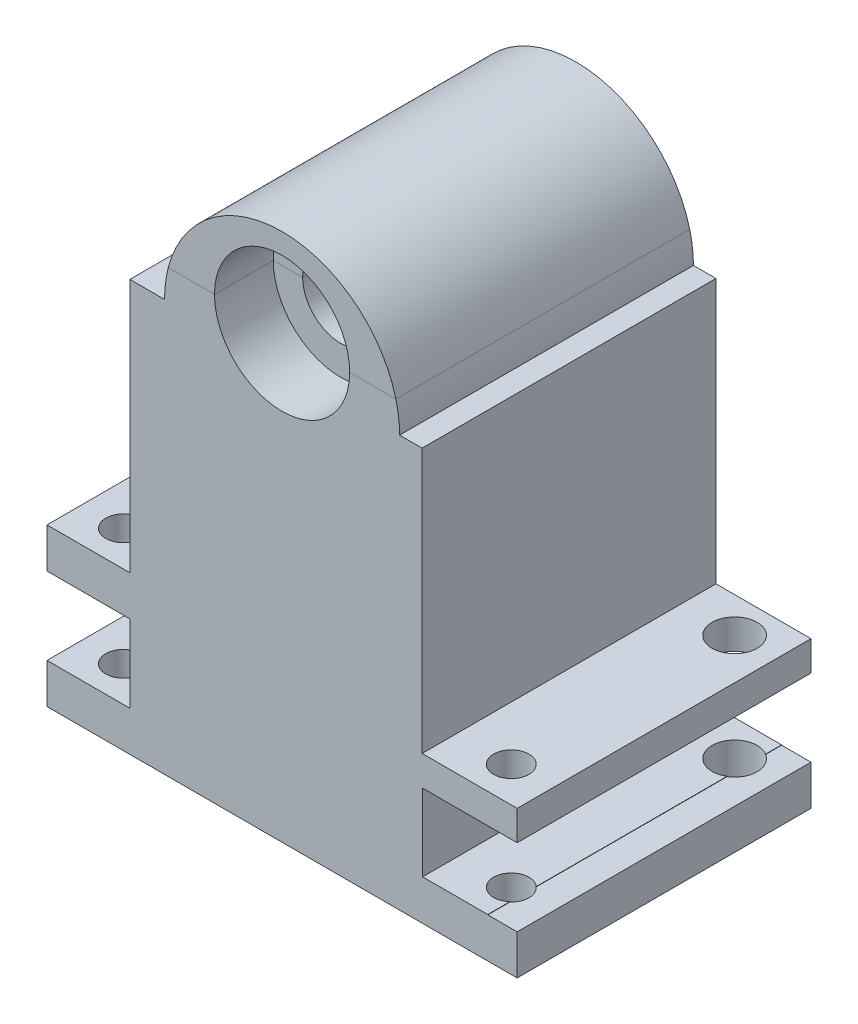
SolidWorks part; units mm, degrees
ref_plane "Plan de face" through (0, 0, 0) normal (0, 0, 1) x (1, 0, 0)
ref_plane "Plan de dessus" through (0, 0, 0) normal (0, 1, 0) x (1, 0, 0)
ref_plane "Plan de droite" through (0, 0, 0) normal (1, 0, 0) x (0, 0, -1)
sketch "Esquisse1" plane through (0, 0, 0) normal (0, 0, 1) x (1, 0, 0)
  line L0 (0, 0) -> (700, 0)
  line L1 (700, 0) -> (700, 450)
  line L2 (700, 450) -> (550, 450)
  line L3 (0, 0) -> (0, 450)
  line L4 (0, 450) -> (150, 450)
  arc A0 (550, 450) -> (150, 450) centre (350, 450) ccw
  dimension "D3" = 200
  dimension "D1" = 700
  dimension "D2" = 450
  dimension "D4" = 150
extrude "Boss.-Extru.1" add sketch "Esquisse1" along normal blind 500
sketch "Esquisse2" plane through (0, 0, 0) normal (0, -1, 0) x (1, 0, 0)
  line L0 (700, 500) -> (700, 0)
  line L1 (700, 0) -> (0, 0)
  line L2 (0, 0) -> (0, 500)
  line L3 (0, 500) -> (700, 500) construction
  line L4 (0, 500) -> (0, 0) construction
  line L5 (0, 500) -> (700, 500)
extrude "Boss.-Extru.2" add sketch "Esquisse2" along normal blind 250
sketch "Esquisse3" plane through (0, 0, 0) normal (0, 0, -1) x (-1, 0, 0)
  circle A0 centre (-350, 500) radius 65
extrude "Enlèv. mat.-Extru.1" cut sketch "Esquisse3" against normal blind 500
sketch "Esquisse4" plane through (0, 0, 0) normal (0, 0, -1) x (-1, 0, 0)
  line L0 (0, -50.3189) -> (-91.0727, -50.3189)
  line L1 (0, 450) -> (0, -250) construction
  line L2 (-91.0727, -50.3189) -> (-91.0727, -181.9886)
  line L3 (-91.0727, -181.9886) -> (0, -181.9886)
  line L4 (0, -181.9886) -> (0, -50.3189)
extrude "Enlèv. mat.-Extru.2" cut sketch "Esquisse4" against normal blind 500
sketch "Esquisse5" plane through (0, 0, 0) normal (0, 0, -1) x (-1, 0, 0)
  line L0 (-700, -181.4044) -> (-589.1123, -181.4044)
  line L1 (-700, -250) -> (-700, 450) construction
  line L2 (-589.1123, -181.4044) -> (-589.1123, -50.6587)
  line L3 (-589.1123, -50.6587) -> (-700, -50.6587)
  line L4 (-700, -50.6587) -> (-700, -181.4044)
extrude "Enlèv. mat.-Extru.3" cut sketch "Esquisse5" against normal blind 500
ref_plane "Plan1" through (0, 500, 0) normal (0, -1, 0) x (-1, 0, 0)
sketch "Esquisse6" plane through (0, 0, 500) normal (0, 0, 1) x (1, 0, 0)
  circle A0 centre (350, 500) radius 115
  circle A1 centre (350, 500) radius 65
extrude "Enlèv. mat.-Extru.4" cut sketch "Esquisse6" against normal blind 100
split "Fractionner2" trim tools "Plan1" bodies to split 108 resulting bodies 109 110
sketch "Esquisse7" plane through (0, 0, 0) normal (0, 0, -1) x (-1, 0, 0)
  circle A0 centre (-350, 500) radius 115
  circle A1 centre (-350, 500) radius 65
extrude "Enlèv. mat.-Extru.5" cut sketch "Esquisse7" against normal blind 100
sketch "Esquisse9" plane through (0, 0, 500) normal (0, 0, 1) x (1, 0, 0)
  line L1 (700, 450) -> (750, 450)
  line L2 (700, 450) -> (700, -50.6587)
  line L3 (700, -50.6587) -> (750, -50.6587)
  line L4 (750, 450) -> (750, -50.6587)
  line L5 (700, -250) -> (750, -250)
  line L6 (700, -250) -> (700, -181.9464)
  line L7 (700, -181.9464) -> (750, -181.9464)
  line L8 (750, -250) -> (750, -181.9464)
  line L9 (0, -50.3189) -> (-50, -50.3189)
  line L10 (0, -50.3189) -> (0, 450)
  line L11 (0, 450) -> (-50, 450)
  line L12 (-50, -50.3189) -> (-50, 450)
  line L13 (0, -181.9886) -> (-50, -181.9886)
  line L14 (0, -181.9886) -> (0, -250)
  line L15 (0, -250) -> (-50, -250)
  line L16 (-50, -181.9886) -> (-50, -250)
  dimension "D1" = 50
  dimension "D2" = 50
extrude "Boss.-Extru.3" add sketch "Esquisse9" against normal blind 500
sketch "Esquisse10" plane through (0, 0, 500) normal (0, 0, 1) x (1, 0, 0)
  line L0 (91.0727, -50.3189) -> (91.0727, 450)
  line L1 (150, 450) -> (-50, 450) construction
  line L2 (91.0727, 450) -> (-50, 450)
  line L3 (-50, 450) -> (-50, 17.6911)
  line L4 (-50, 450) -> (-50, -50.3189) construction
  line L5 (-50, 17.6911) -> (91.0727, 17.6911)
  line L8 (750, 0) -> (588.2822, 0)
  line L9 (750, -50.6587) -> (750, 450) construction
  line L10 (588.2822, 0) -> (588.2822, 450)
  line L11 (750, 450) -> (550, 450) construction
  line L12 (588.2822, 450) -> (750, 450)
  line L13 (750, 450) -> (750, 0)
  line M3 (150, 450) -> (-50, 450)
  line M4 (-50, 450) -> (-50, -50.3189)
  line M16 (750, -50.6587) -> (750, 450)
  line M17 (750, 450) -> (550, 450)
  dimension "D1" = 68.01
extrude "Enlèv. mat.-Extru.6" cut sketch "Esquisse10" against normal blind 500 contours L10 L8 M16 M17 | L5 L0 M4 M3 region at (20.5364, 233.8456, 500) region at (669.1411, 225, 500)
sketch "Esquisse11" plane through (0, 17.6911, 0) normal (0, 1, 0) x (1, 0, 0)
  line L0 (-50, 0) -> (91.0727, 0) construction
  line L1 (-50, 0) -> (-50, -500) construction
  line L2 (-50, -500) -> (91.0727, -500) construction
  circle A0 centre (20, -60) radius 30
  circle A1 centre (20, -440) radius 30
  point P8 (0, 0)
  dimension "D1" = 60
  dimension "D3" = 70
  dimension "D2" = 70
  dimension "D4" = 60
extrude "Enlèv. mat.-Extru.7" cut sketch "Esquisse11" against normal blind 310
sketch "Esquisse12" plane through (0, 0, 0) normal (0, 1, 0) x (1, 0, 0)
  line L0 (750, 0) -> (588.2822, 0) construction
  line L1 (750, 0) -> (750, -500) construction
  line L2 (750, -500) -> (588.2822, -500) construction
  circle A0 centre (680, -60) radius 38.3342
  circle A1 centre (680, -440) radius 30
  dimension "D3" = 60
  dimension "D1" = 60
  dimension "D2" = 70
extrude "Enlèv. mat.-Extru.8" cut sketch "Esquisse12" against normal blind 310
